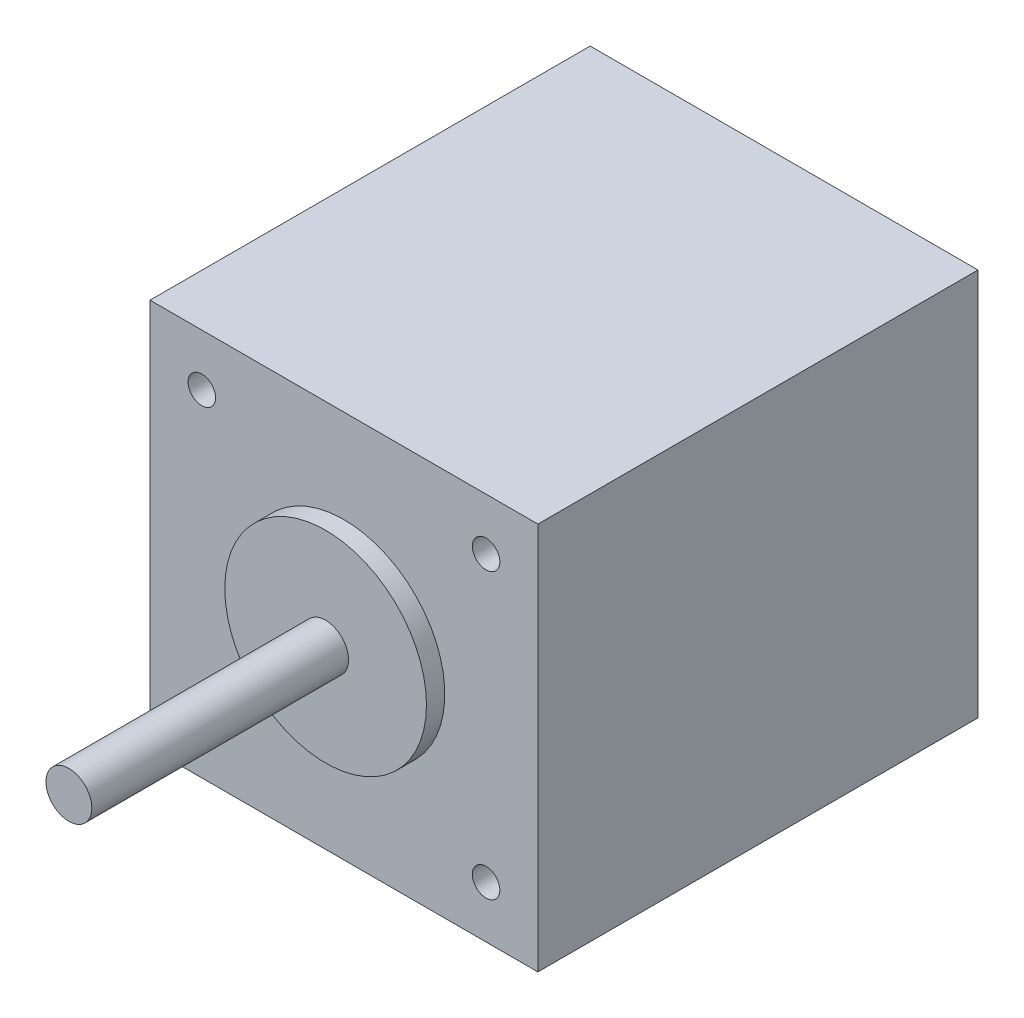
SolidWorks part; units mm, degrees
ref_plane "Спереди" through (0, 0, 0) normal (0, 0, 1) x (1, 0, 0)
ref_plane "Сверху" through (0, 0, 0) normal (0, 1, 0) x (1, 0, 0)
ref_plane "Справа" through (0, 0, 0) normal (1, 0, 0) x (0, 0, -1)
other "Configuration Table"
sketch "Эскиз1" plane through (0, 0, 0) normal (0, 0, 1) x (1, 0, 0)
  line L1 (-21.15, -21.15) -> (21.15, -21.15)
  line L2 (-21.15, -21.15) -> (-21.15, 21.15)
  line L3 (-21.15, 21.15) -> (21.15, 21.15)
  line L4 (21.15, -21.15) -> (21.15, 21.15)
  line L5 (-21.15, -21.15) -> (21.15, 21.15) construction
  line L6 (-21.15, 21.15) -> (21.15, -21.15) construction
  point P0 (0, 0)
  dimension "D1" = 42.3
  dimension "D2" = 42.3
extrude "Корпус" add sketch "Эскиз1" along normal blind 48
sketch "Эскиз2" plane through (0, 0, 0) normal (0, 0, 1) x (1, 0, 0)
  circle A0 centre (0, 0) radius 2.5
extrude "Вал_ПРЕДВ" add sketch "Эскиз2" along normal blind 78
sketch "Эскиз3" plane through (0, 0, 0) normal (0, 0, 1) x (1, 0, 0)
  circle A0 centre (0, 0) radius 11
  dimension "D1" = 22
extrude "Буртик_ПРЕДВ" add sketch "Эскиз3" along normal blind 50
sketch "Эскиз4" plane through (0, 0, 0) normal (0, 0, 1) x (1, 0, 0)
  circle A0 centre (0, 0) radius 8
  dimension "D1" = 16
sketch "Эскиз5" plane through (0, 0, 0) normal (0, 0, 1) x (1, 0, 0)
  circle A0 centre (-15.5, -15.5) radius 1.5
  circle A1 centre (-15.5, 15.5) radius 1.5
  circle A2 centre (15.5, -15.5) radius 1.5
  circle A3 centre (15.5, 15.5) radius 1.5
  dimension "D2" = 3
  dimension "D3" = 3
  dimension "D4" = 3
extrude "Крепеж_М3_ПРЕДВ" cut sketch "Эскиз5" against normal blind 4.5 from offset 48
equation "\"Мотор X ширина корпуса\"= 42.3"
equation "\"Мотор X высота корпуса\"= 42.3"
equation "\"Мотор X длина корпуса\"= 40"
equation "\"Мотор X вылет вала\"= 19.8"
equation "\"Мотор Y ширина корпуса\"= 42.3"
equation "\"Мотор Y высота корпуса\"= 42.3"
equation "\"Мотор Y длина корпуса\"= 48"
equation "\"Мотор Y вылет вала\"= 30"
equation "\"Мотор Z ширина корпуса\"= 42"
equation "\"Мотор Z высота корпуса\"= 42"
equation "\"Мотор Z длина корпуса\"= 40"
equation "\"Мотор Z вылет вала\"= 23"
equation "\"Мотор диаметр вала ПРЕДВ\"= 5"
equation "\"Мотор шаг крепления ПРЕДВ\"= 31"
equation "\"Мотор диаметр отверстий ПРЕДВ\"= 3"
equation "\"Мотор глубина отверстий ПРЕДВ\"= 4.5"
equation "\"Мотор диаметр буртика ПРЕДВ\"= 22"
equation "\"Мотор высота буртика ПРЕДВ\"= 2"
equation "\"Мотор диаметр шкива ПРЕДВ\"= 16"
equation "\"Мотор длина шкива ПРЕДВ\"= 12"
equation "\"Мотор отступ шкива ПРЕДВ\"= 5"
equation "\"Мотор X шаг градусов\"= 1.8"
equation "\"Мотор Y шаг градусов\"= 1.8"
equation "\"Мотор Z шаг градусов\"= 1.8"
equation "\"Мотор Y диаметр ротора\"= 25.78"
equation "\"D1@Эскиз1\" = \"Мотор Y ширина корпуса\""
equation "\"D1@Корпус\" = \"Мотор Y длина корпуса\""
equation "\"D1@Эскиз2\" = \"Мотор диаметр вала ПРЕДВ\""
equation "\"D1@Вал_ПРЕДВ\" = \"Мотор Y длина корпуса\" + \"Мотор Y вылет вала\""
equation "\"D1@Эскиз3\" = \"Мотор диаметр буртика ПРЕДВ\""
equation "\"D1@Буртик_ПРЕДВ\" = \"Мотор Y длина корпуса\" + \"Мотор высота буртика ПРЕДВ\""
equation "\"D1@Эскиз4\" = \"Мотор диаметр шкива ПРЕДВ\""
equation "\"D1@Эскиз5\" = \"Мотор диаметр отверстий ПРЕДВ\""
equation "\"D2@Эскиз5\" = \"Мотор диаметр отверстий ПРЕДВ\""
equation "\"D3@Эскиз5\" = \"Мотор диаметр отверстий ПРЕДВ\""
equation "\"D4@Эскиз5\" = \"Мотор диаметр отверстий ПРЕДВ\""
equation "\"D1@Крепеж_М3_ПРЕДВ\" = \"Мотор глубина отверстий ПРЕДВ\""
equation "\"D19@Крепеж_М3_ПРЕДВ\" = \"Мотор Y длина корпуса\""
equation "\"Ширина груза\"= 420"
equation "\"Глубина груза\"= 490"
equation "\"Высота груза\"= 297"
equation "\"Ширина ячейки\"= \"Ширина груза\" + 10"
equation "\"Глубина ячейки\"= \"Глубина груза\" + 10"
equation "\"Высота ячейки\"= \"Высота груза\" + 10 + 13"
equation "\"Колво ячеек ширина\"= 2"
equation "\"Колво ячеек высота\"= 2"
equation "\"Толщина стенки\"= 10"
equation "\"Крепление дверцы\"= 5"
equation "\"Ширина рейки\"= \"Толщина шестерни\""
equation "\"Высота рейки\"= 20"
equation "\"Высота пола\"= 20"
equation "\"Колво полозьев\"= 5"
equation "\"Отступ рейки\"= 20"
equation "\"Глубина каретки\"= \"Глубина ячейки\" + 30 + \"Мотор Y высота корпуса\" + 20"
equation "\"Отступ шпильки\"= 20"
equation "\"Диаметр шпильки\"= 5"
equation "\"Длинна шпильки\"= ( \"Высота ячейки\" + \"Толщина стенки\" + \"Высота пола\" ) * \"Колво ячеек высота\" + ( \"Толщина стенки\" + \"Отступ рейки\" ) * 2 "
equation "\"Ширина пластины\"= 50  "
equation "\"Высота зона выгрузки\"= \"Высота ячейки\" * 2 + \"Толщина стенки\" * 2"
equation "\"Колво выгрузки\"= 1"
equation "\"Отступ крепления мотора фиксации\" = 30"
equation "\"Ширина ячейки выгрузки\"= \"Ширина ячейки\" + \"Толщина стенки\" + \"Отступ крепления мотора фиксации\"*2"
equation "\"Длинна рейки\"= ( \"Ширина ячейки\" + \"Толщина стенки\" + \"Крепление дверцы\" ) * \"Колво ячеек ширина\" + \"Ширина ячейки выгрузки\" * \"Колво выгрузки\" + \"Толщина стенки\""
equation "\"Толщина шестерни\"= 10"
